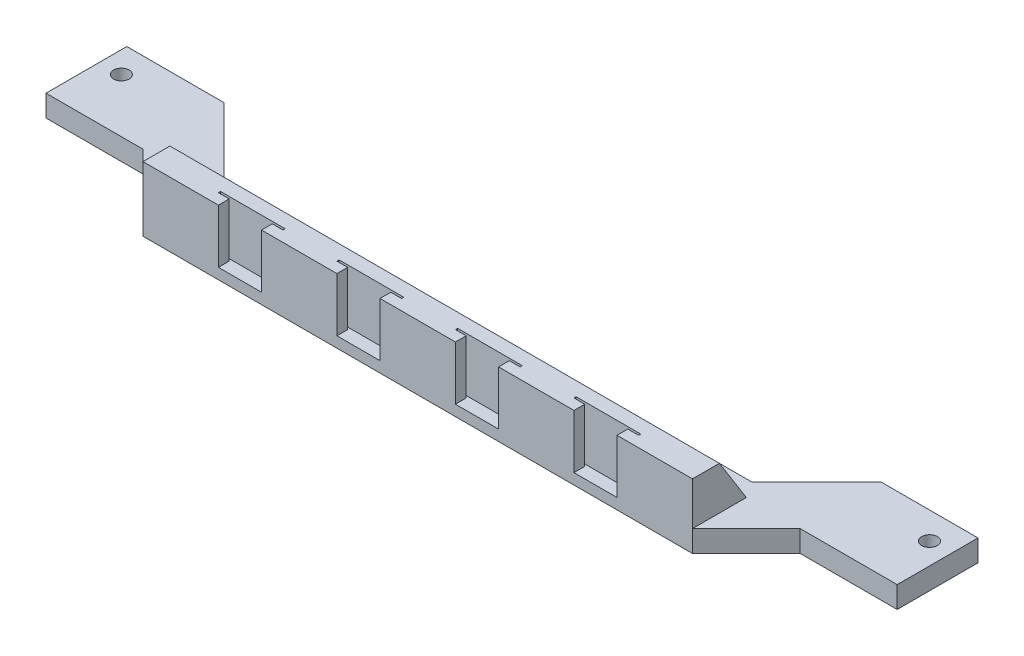
SolidWorks part; units mm, degrees
ref_plane "前视基准面" through (0, 0, 0) normal (0, 0, 1) x (1, 0, 0)
ref_plane "上视基准面" through (0, 0, 0) normal (0, 1, 0) x (1, 0, 0)
ref_plane "右视基准面" through (0, 0, 0) normal (1, 0, 0) x (0, 0, -1)
other "Configuration Table"
sketch "草图1" plane through (0, 0, 0) normal (0, 1, 0) x (1, 0, 0)
  line L1 (80, -12.5) -> (-80, -12.5)
  line L2 (80, -12.5) -> (80, 12.5)
  line L3 (80, 12.5) -> (-80, 12.5)
  line L4 (-80, -12.5) -> (-80, 12.5)
  line L5 (80, -12.5) -> (-80, 12.5) construction
  line L6 (80, 12.5) -> (-80, -12.5) construction
  point P0 (0, 0)
  dimension "D1" = 160
  dimension "D2" = 25
extrude "凸台-拉伸1" add sketch "草图1" along normal blind 4
sketch "草图3" plane through (0, 4, 0) normal (0, 1, 0) x (1, 0, 0)
  line L0 (-80, 12.5) -> (-80, -12.5) construction
  line L1 (80, 12.5) -> (-80, 12.5) construction
  circle A0 centre (-75, 7.5) radius 1.45
  circle A1 centre (75, 7.5) radius 1.45
  dimension "D1" = 5
  dimension "D2" = 150
  dimension "D3" = 2.9
  dimension "D4" = 2.9
  dimension "D5" = 5
  dimension "D6" = 5
extrude "切除-拉伸1" cut sketch "草图3" against normal blind 4
sketch "草图5" plane through (0, 4, 0) normal (0, 1, 0) x (1, 0, 0)
  line L0 (-80, -12.5) -> (80, -12.5) construction
  line L1 (-51, -12.5) -> (51, -12.5)
  line L2 (-51, -12.5) -> (-51, -2.5)
  line L3 (-51, -2.5) -> (51, -2.5)
  line L4 (51, -12.5) -> (51, -2.5)
  line L5 (-80, 12.5) -> (-80, -12.5) construction
  dimension "D1" = 102
  dimension "D2" = 29
  dimension "D3" = 10
extrude "凸台-拉伸2" add sketch "草图5" along normal blind 8
sketch "草图6" plane through (0, 4, 0) normal (0, 1, 0) x (1, 0, 0)
  line L1 (-51, -2.5) -> (-80, -2.5)
  line L2 (-51, -2.5) -> (-51, -12.5)
  line L3 (-51, -12.5) -> (-80, -12.5)
  line L4 (-80, -2.5) -> (-80, -12.5)
  line L5 (51, -2.5) -> (80, -2.5)
  line L6 (51, -2.5) -> (51, -12.5)
  line L7 (51, -12.5) -> (80, -12.5)
  line L8 (80, -2.5) -> (80, -12.5)
extrude "切除-拉伸2" cut sketch "草图6" against normal blind 6
chamfer "倒角1" distance 10 angle 45 2 edges at (51, 2, 2.5) (-51, 2, 2.5)
sketch "草图7" plane through (0, 12, 0) normal (0, 1, 0) x (1, 0, 0)
  line L0 (-51, -2.5) -> (-51, -12.5) construction
  line L1 (-39, -10.1) -> (-27, -10.1)
  line L2 (-39, -10.1) -> (-39, -10.5)
  line L3 (-39, -10.5) -> (-37, -10.5)
  line L4 (-27, -10.1) -> (-27, -10.5)
  line L5 (-17, -10.1) -> (-5, -10.1)
  line L6 (-17, -10.1) -> (-17, -10.5)
  line L7 (-17, -10.5) -> (-15, -10.5)
  line L8 (-5, -10.1) -> (-5, -10.5)
  line L9 (5, -10.1) -> (17, -10.1)
  line L10 (5, -10.1) -> (5, -10.5)
  line L11 (5, -10.5) -> (7, -10.5)
  line L12 (17, -10.1) -> (17, -10.5)
  line L13 (27, -10.1) -> (39, -10.1)
  line L14 (27, -10.1) -> (27, -10.5)
  line L15 (27, -10.5) -> (29, -10.5)
  line L16 (39, -10.1) -> (39, -10.5)
  line L19 (-51, -12.5) -> (51, -12.5) construction
  line L20 (37, -10.5) -> (39, -10.5)
  line L22 (-37, -10.5) -> (-37, -12.5)
  line L23 (-37, -12.5) -> (-29, -12.5)
  line L24 (-29, -10.5) -> (-29, -12.5)
  line L26 (-15, -10.5) -> (-15, -12.5)
  line L27 (-15, -12.5) -> (-7, -12.5)
  line L28 (-7, -10.5) -> (-7, -12.5)
  line L30 (7, -10.5) -> (7, -12.5)
  line L31 (7, -12.5) -> (15, -12.5)
  line L32 (15, -10.5) -> (15, -12.5)
  line L34 (29, -10.5) -> (29, -12.5)
  line L35 (29, -12.5) -> (37, -12.5)
  line L36 (37, -10.5) -> (37, -12.5)
  line L37 (15, -10.5) -> (17, -10.5)
  line L38 (-7, -10.5) -> (-5, -10.5)
  line L39 (-29, -10.5) -> (-27, -10.5)
  dimension "D1" = 12
  dimension "D2" = 12
  dimension "D3" = 10
  dimension "D4" = 12
  dimension "D5" = 10
  dimension "D6" = 12
  dimension "D7" = 10
  dimension "D8" = 12
  dimension "D9" = 0.4
  dimension "D10" = 0.4
  dimension "D11" = 0.4
  dimension "D12" = 0.4
  dimension "D13" = 2
  dimension "D14" = 2
  dimension "D15" = 2
  dimension "D16" = 2
  dimension "D17" = 2
  dimension "D18" = 2
  dimension "D19" = 2
  dimension "D20" = 2
  dimension "D21" = 2
  dimension "D22" = 2
  dimension "D23" = 2
  dimension "D24" = 2
extrude "切除-拉伸3" cut sketch "草图7" against normal blind 10
sketch "草图9" plane through (-51, 0, 0) normal (-1, 0, 0) x (0, 0, 1)
  line L0 (7.5, 12) -> (2.5, 4)
  line L1 (2.5, 12) -> (12.5, 12) construction
  line L2 (2.5, 4) -> (2.5, 12)
  line L3 (2.5, 12) -> (7.5, 12)
extrude "切除-拉伸4" cut sketch "草图9" against normal blind 142
sketch "草图10" plane through (0, 4, 0) normal (0, 1, 0) x (1, 0, 0)
  line L0 (80, 12.5) -> (-80, 12.5) construction
  line L1 (-61, 12.5) -> (61, 12.5)
  line L2 (-61, 12.5) -> (-61, 0.5)
  line L3 (-61, 0.5) -> (61, 0.5)
  line L4 (61, 12.5) -> (61, 0.5)
  dimension "D1" = 12
extrude "切除-拉伸5" cut sketch "草图10" against normal blind 142
chamfer "倒角2" distance 12 angle 45 2 edges at (-61, 2, -0.5) (61, 2, -0.5)
sketch "草图11" plane through (-80, 0, 0) normal (-1, 0, 0) x (0, 0, 1)
  line L4 (-12.5, 0) -> (2.5, 0)
  line L5 (2.5, 0) -> (2.5, 4)
  line L6 (2.5, 4) -> (-12.5, 4)
  line L7 (-12.5, 4) -> (-12.5, 0)
  line L8 (-12.5, 0) -> (2.5, 0)
  line L9 (2.5, 0) -> (2.5, 4)
  line L10 (2.5, 4) -> (-12.5, 4)
  line L11 (-12.5, 4) -> (-12.5, 0)
  dimension "D1" = 0
extrude "切除-拉伸6" cut sketch "草图11" against normal blind 1
sketch "草图12" plane through (80, 0, 0) normal (1, 0, 0) x (0, 0, -1)
  line L4 (12.5, 4) -> (-2.5, 4)
  line L5 (-2.5, 4) -> (-2.5, 0)
  line L6 (-2.5, 0) -> (12.5, 0)
  line L7 (12.5, 0) -> (12.5, 4)
  line L8 (12.5, 4) -> (-2.5, 4)
  line L9 (-2.5, 4) -> (-2.5, 0)
  line L10 (-2.5, 0) -> (12.5, 0)
  line L11 (12.5, 0) -> (12.5, 4)
  dimension "D1" = 0
extrude "切除-拉伸7" cut sketch "草图12" against normal blind 1
